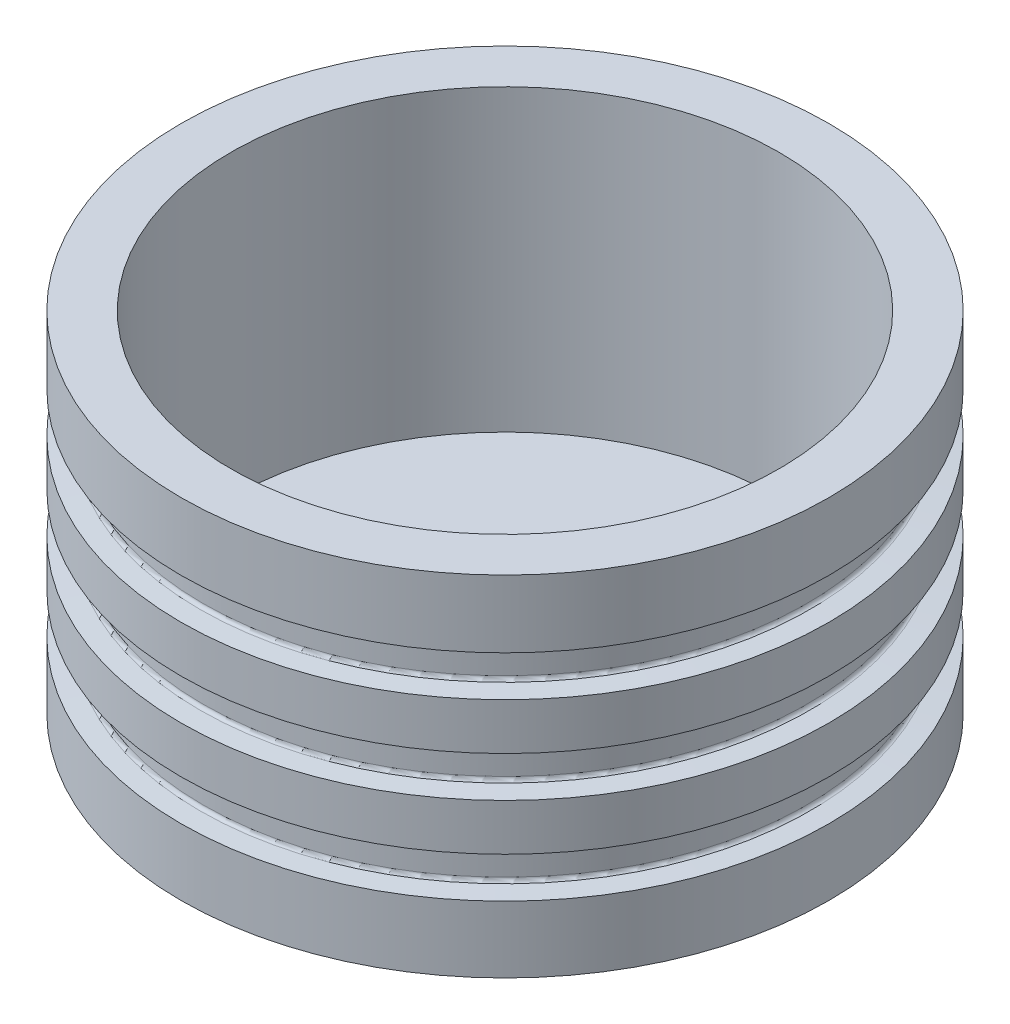
SolidWorks part; units mm, degrees
material "1060 Alloy"
ref_plane "Front Plane" through (0, 0, 0) normal (0, 0, 1) x (1, 0, 0)
ref_plane "Top Plane" through (0, 0, 0) normal (0, 1, 0) x (1, 0, 0)
ref_plane "Right Plane" through (0, 0, 0) normal (1, 0, 0) x (0, 0, -1)
sketch "Sketch1" plane through (0, 0, 0) normal (0, 0, 1) x (1, 0, 0)
  line L0 (0, 0) -> (0, 44.45) construction
  line L1 (-41.275, 0) -> (-41.275, 44.45)
  line L2 (-41.275, 0) -> (-6.35, 0)
  line L3 (-2.8209, 0) -> (-2.8209, 6.35)
  line L4 (-2.8209, 6.35) -> (-34.925, 6.35)
  line L5 (-34.925, 6.35) -> (-34.925, 44.45)
  line L6 (-34.925, 44.45) -> (-41.275, 44.45)
  line L7 (-2.8209, 0) -> (-2.8209, -12.7)
  line L8 (-2.8209, -12.7) -> (-6.35, -12.7)
  line L9 (-6.35, -12.7) -> (-6.35, 0)
  dimension "D1" = 44.45
  dimension "D2" = 2.8209
  dimension "D3" = 41.275
  dimension "D4" = 6.35
  dimension "D5" = 6.35
  dimension "D6" = 12.7
  dimension "D7" = 6.35
revolve "Revolve1" add sketch "Sketch1" angle 360 about L0
ref_plane "Plane1" through (0, 0, 0) normal (-1, 0, 0) x (0, 0, -1)
sketch "Sketch3" plane through (0, 0, 0) normal (-1, 0, 0) x (0, 0, -1)
  line L0 (38.8614, -27.1337) -> (41.3639, -26.9147)
  line L1 (41.3639, -26.9147) -> (41.3639, -32.1024)
  line L2 (41.3639, -32.1024) -> (38.8614, -31.8835)
  line L3 (38.4556, -31.4407) -> (38.4556, -27.5765)
  line L4 (0, 50) -> (0, -50) construction
  arc A0 (38.8614, -31.8835) -> (38.4556, -31.4407) centre (38.9001, -31.4407) cw
  arc A1 (38.4556, -27.5765) -> (38.8614, -27.1337) centre (38.9001, -27.5765) cw
ref_plane "Plane2" through (0, 0, 0) normal (-1, 0, 0) x (0, 0, -1)
sketch "Sketch5" plane through (0, 0, 0) normal (-1, 0, 0) x (0, 0, -1)
  line L0 (38.8614, -30.9088) -> (41.3639, -30.6898)
  line L1 (41.3639, -30.6898) -> (41.3639, -35.8775)
  line L2 (41.3639, -35.8775) -> (38.8614, -35.6586)
  line L3 (38.4556, -35.2157) -> (38.4556, -31.3516)
  line L4 (0, 50) -> (0, -50) construction
  line L5 (0, 50) -> (0, -50) construction
  line L6 (-41.275, -44.45) -> (41.275, -44.45) construction
  arc A0 (38.8614, -35.6586) -> (38.4556, -35.2157) centre (38.9001, -35.2157) cw
  arc A1 (38.4556, -31.3516) -> (38.8614, -30.9088) centre (38.9001, -31.3516) cw
  dimension "D1" = 8.5725
revolve "Groove for AS 568-234, O-Ring1" cut sketch "Sketch5"
ref_plane "Plane3" through (0, 0, 0) normal (-1, 0, 0) x (0, 0, -1)
sketch "Sketch7" plane through (0, 0, 0) normal (-1, 0, 0) x (0, 0, -1)
  line L0 (38.8614, -19.7963) -> (41.3639, -19.5773)
  line L1 (41.3639, -19.5773) -> (41.3639, -24.765)
  line L2 (41.3639, -24.765) -> (38.8614, -24.5461)
  line L3 (38.4556, -24.1032) -> (38.4556, -20.2391)
  line L4 (0, 50) -> (0, -50) construction
  line L5 (0, 50) -> (0, -50) construction
  line L6 (-41.275, -44.45) -> (41.275, -44.45) construction
  arc A0 (38.8614, -24.5461) -> (38.4556, -24.1032) centre (38.9001, -24.1032) cw
  arc A1 (38.4556, -20.2391) -> (38.8614, -19.7963) centre (38.9001, -20.2391) cw
  dimension "D1" = 19.685
revolve "Groove for AS 568-234, O-Ring2" cut sketch "Sketch7" angle 360 about L4 reverse direction yes
ref_plane "Plane4" through (0, 0, 0) normal (-1, 0, 0) x (0, 0, -1)
sketch "Sketch9" plane through (0, 0, 0) normal (-1, 0, 0) x (0, 0, -1)
  line L0 (38.8614, -8.6838) -> (41.3639, -8.4648)
  line L1 (41.3639, -8.4648) -> (41.3639, -13.6525)
  line L2 (41.3639, -13.6525) -> (38.8614, -13.4336)
  line L3 (38.4556, -12.9907) -> (38.4556, -9.1266)
  line L4 (0, 50) -> (0, -50) construction
  line L5 (0, 50) -> (0, -50) construction
  line L6 (-41.275, -44.45) -> (41.275, -44.45) construction
  arc A0 (38.8614, -13.4336) -> (38.4556, -12.9907) centre (38.9001, -12.9907) cw
  arc A1 (38.4556, -9.1266) -> (38.8614, -8.6838) centre (38.9001, -9.1266) cw
  dimension "D1" = 30.7975
revolve "Groove for AS 568-234, O-Ring3" cut sketch "Sketch9" angle 360 about L4 reverse direction yes
